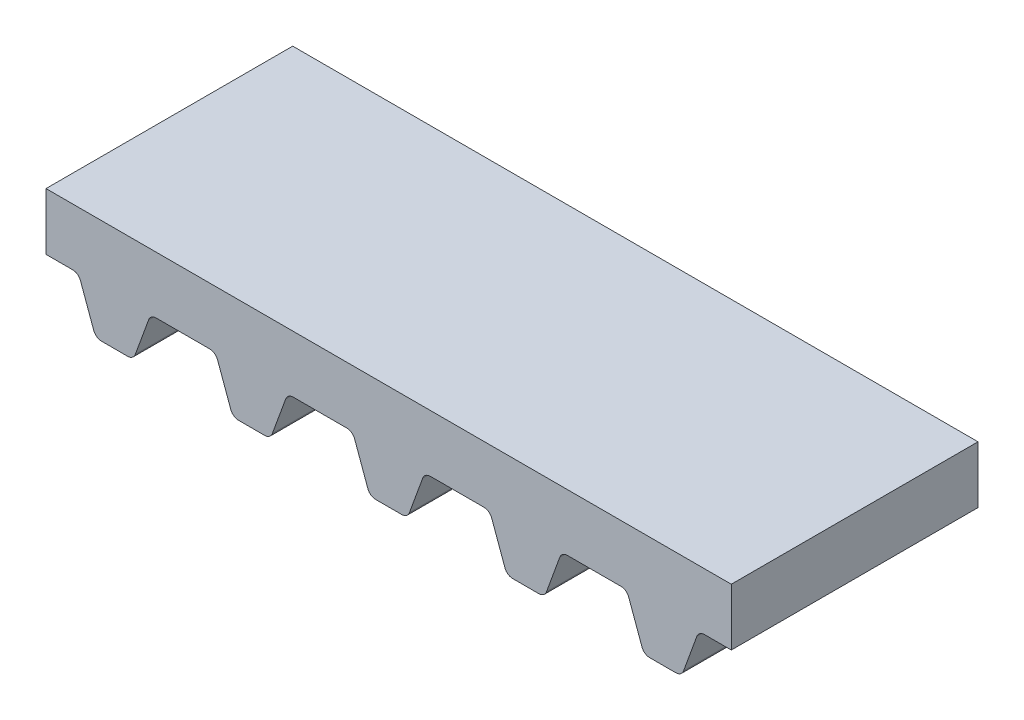
SolidWorks part; units mm, degrees
ref_plane "Front Plane" through (0, 0, 0) normal (0, 0, 1) x (1, 0, 0)
ref_plane "Top Plane" through (0, 0, 0) normal (0, 1, 0) x (1, 0, 0)
ref_plane "Right Plane" through (0, 0, 0) normal (1, 0, 0) x (0, 0, -1)
sketch "Sketch1" plane through (0, 0, 0) normal (0, 0, 1) x (1, 0, 0)
  line L0 (0, 0) -> (5, 0)
  line L1 (0, 0) -> (0, -2.08)
  line L2 (0, -2.08) -> (1.1852, -2.08)
  line L3 (5, 0) -> (5, -2.08)
  line L5 (1.8148, -3.81) -> (3.1852, -3.81)
  line L6 (1.1852, -2.08) -> (1.8148, -3.81)
  line L7 (2.5, -9.1246) -> (2.5, 4.774) construction
  line L8 (5, -2.08) -> (3.8148, -2.08)
  line L9 (3.8148, -2.08) -> (3.1852, -3.81)
  point P7 (1.5, -2.945)
  dimension "D2" = 2.08
  dimension "D3" = 1
  dimension "D5" = 3.81
  dimension "D6" = 2.5
  dimension "D7" = 20
extrude "Boss-Extrude1" add sketch "Sketch1" along normal mid plane 9
fillet "Fillet1" radius 0.3 4 edges at (1.8148, -3.81, 0) (1.1852, -2.08, 0) (3.1852, -3.81, 0) (3.8148, -2.08, 0)
ref_axis "Axis1" through (-0.4, 0, 0) along (1, 0, 0)
pattern_linear "LPattern1" count 5 spacing 5 along (1, 0, 0) of "Boss-Extrude1", "Fillet1"
sketch "Sketch3" plane through (0, 0, 0) normal (0, 0, 1) x (1, 0, 0)
  line L0 (-2.5996, -4.3) -> (56.4484, -4.3) construction
  dimension "D1" = 4.3
